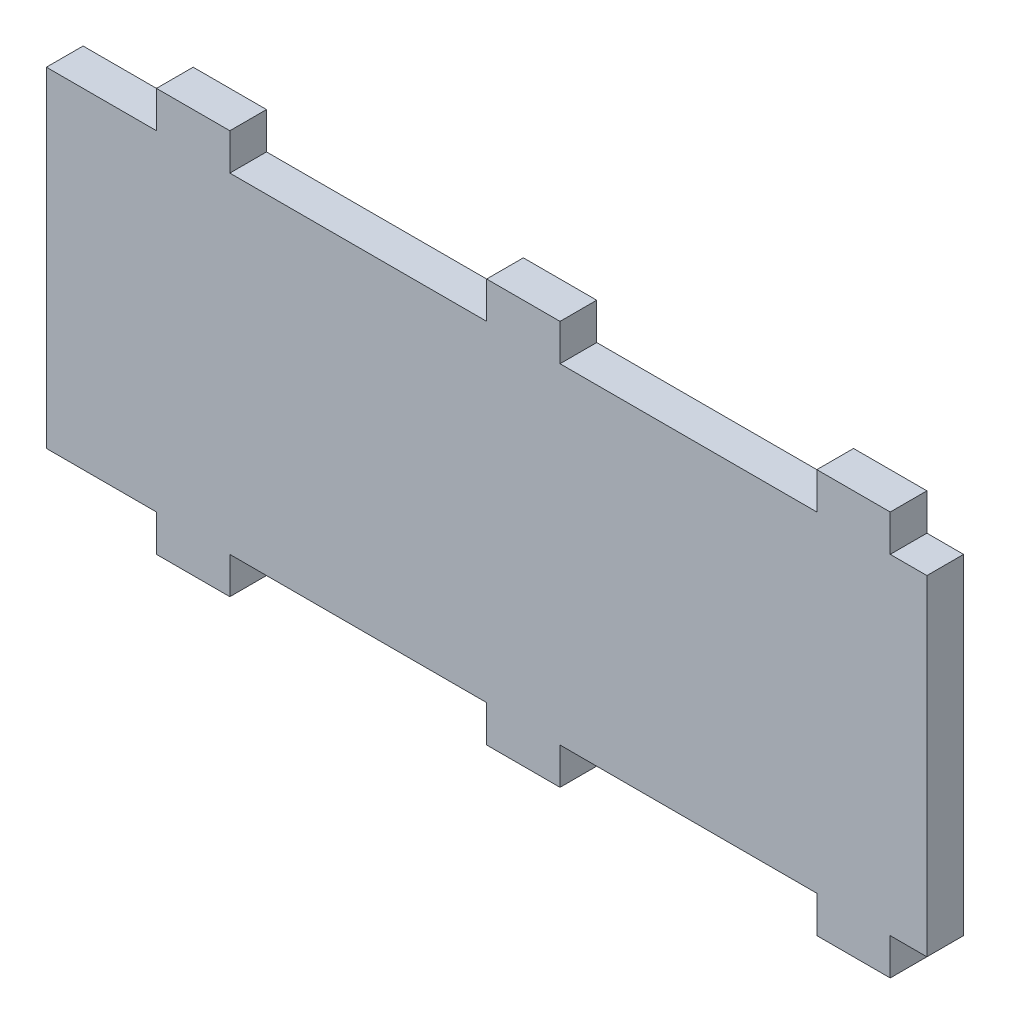
SolidWorks part; units mm, degrees
ref_plane "Plan de face" through (0, 0, 0) normal (0, 0, 1) x (1, 0, 0)
ref_plane "Plan de dessus" through (0, 0, 0) normal (0, 1, 0) x (1, 0, 0)
ref_plane "Plan de droite" through (0, 0, 0) normal (1, 0, 0) x (0, 0, -1)
sketch "Esquisse1" plane through (0, 0, 0) normal (0, 0, 1) x (1, 0, 0)
  line L0 (0, 22.5) -> (120, 22.5) construction
  line L1 (0, 0) -> (15, 0)
  line L2 (0, 0) -> (0, 45)
  line L3 (0, 45) -> (15, 45)
  line L4 (120, 0) -> (120, 45)
  line L5 (60, 0) -> (60, -5)
  line L6 (70, 0) -> (105, 0)
  line L7 (15, 0) -> (15, -5)
  line L8 (15, -5) -> (25, -5)
  line L9 (25, 0) -> (25, -5)
  line L10 (115, 0) -> (120, 0)
  line L11 (70, 0) -> (70, -5)
  line L12 (60, -5) -> (70, -5)
  line L13 (105, 0) -> (105, -5)
  line L14 (115, 45) -> (115, 50)
  line L15 (115, 0) -> (115, -5)
  line L16 (105, -5) -> (115, -5)
  line L17 (25, 0) -> (60, 0)
  line L18 (105, 50) -> (115, 50)
  line L19 (105, 45) -> (105, 50)
  line L20 (70, 45) -> (70, 50)
  line L21 (60, 50) -> (70, 50)
  line L22 (60, 45) -> (60, 50)
  line L23 (25, 45) -> (25, 50)
  line L24 (15, 50) -> (25, 50)
  line L25 (15, 45) -> (15, 50)
  line L26 (25, 45) -> (60, 45)
  line L27 (70, 45) -> (105, 45)
  line L28 (115, 45) -> (120, 45)
  dimension "D1" = 45
  dimension "D2" = 120
  dimension "D3" = 5
  dimension "D4" = 10
  dimension "D5" = 15
  dimension "D7" = 35
  dimension "D6" = 35
extrude "Boss.-Extru.1" add sketch "Esquisse1" along normal blind 5
